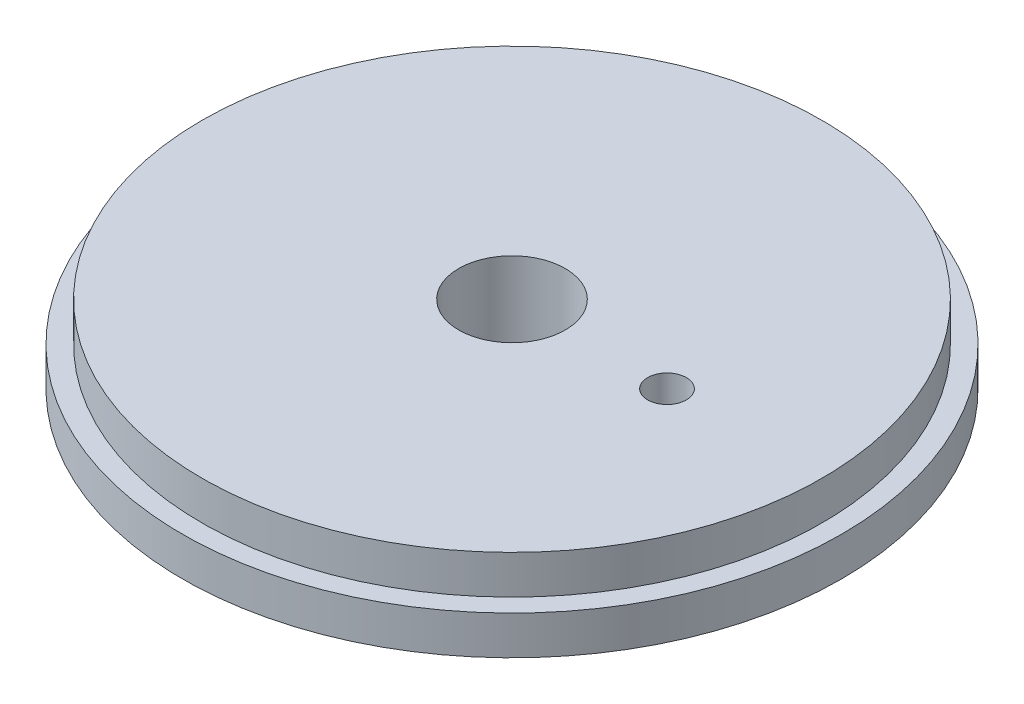
SolidWorks part; units mm, degrees
ref_plane "Front Plane" through (0, 0, 0) normal (0, 0, 1) x (1, 0, 0)
ref_plane "Top Plane" through (0, 0, 0) normal (0, 1, 0) x (1, 0, 0)
ref_plane "Right Plane" through (0, 0, 0) normal (1, 0, 0) x (0, 0, -1)
sketch "Sketch1" plane through (0, 0, 0) normal (0, 0, 1) x (1, 0, 0)
  line L0 (0, 0) -> (-27, 0)
  line L1 (-27, 0) -> (-27, 3.175)
  line L2 (-27, 3.175) -> (-25.4, 3.175)
  line L3 (-25.4, 3.175) -> (-25.4, 6.35)
  line L4 (-25.4, 6.35) -> (0, 6.35)
  line L5 (0, 6.35) -> (0, 0)
  dimension "D1" = 27
  dimension "D2" = 6.35
  dimension "D3" = 1.6
ref_axis "Axis1" through (0, 6.6675, 0) along (0, -1, 0)
revolve "Revolve1" add sketch "Sketch1" angle 360 about L5
sketch "Sketch2" plane through (0, 6.35, 0) normal (0, 1, 0) x (1, 0, 0)
  circle A0 centre (0, 0) radius 4.3656
  circle A1 centre (12.7, 0) radius 1.5875
  point P5 (0, 0)
  point P6 (0, 0)
  dimension "D1" = 8.7312
  dimension "D2" = 3.175
  dimension "D3" = 12.7
extrude "Cut-Extrude1" cut sketch "Sketch2" against normal through all both and the other way through all
sketch "Sketch3" plane through (0, 0, 0) normal (0, -1, 0) x (1, 0, 0)
  circle A0 centre (0, 12.7) radius 3.9688
  point P2 (0, 0)
  dimension "D1" = 7.9375
  dimension "D2" = 12.7
extrude "Cut-Extrude2" cut sketch "Sketch3" against normal blind 3.175
